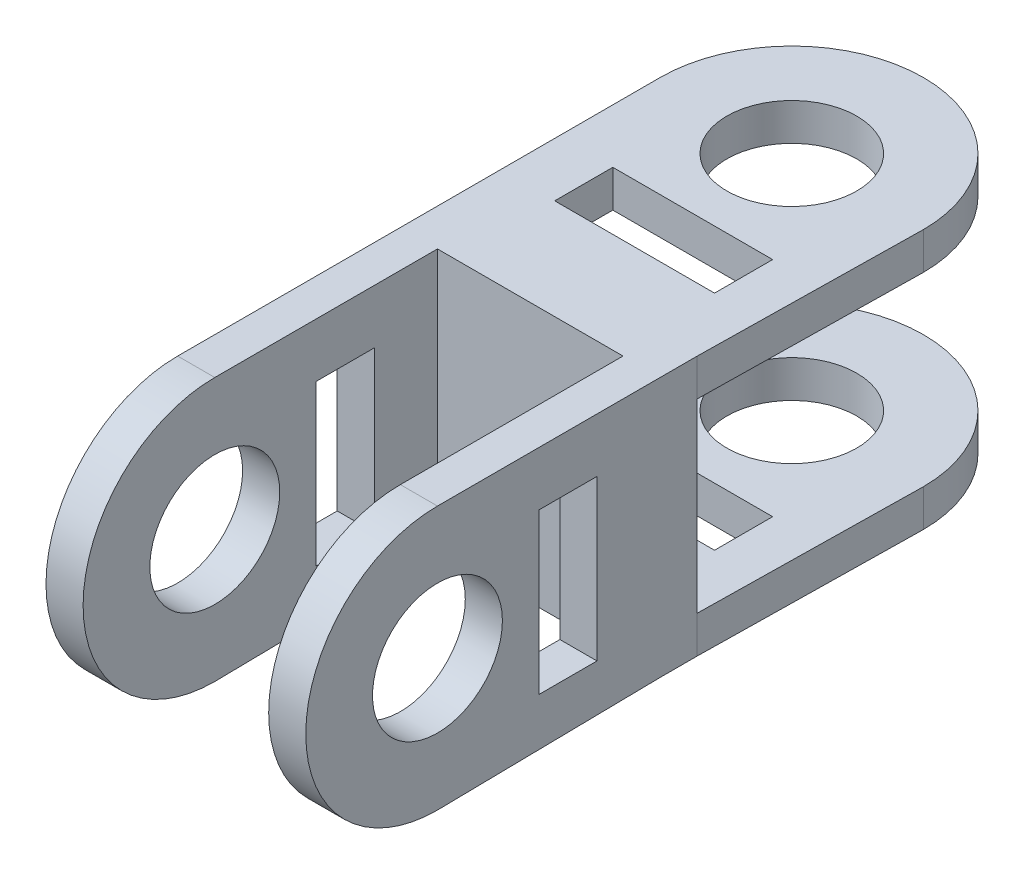
SolidWorks part; units mm, degrees
ref_plane "前基準面" through (0, 0, 0) normal (0, 0, 1) x (1, 0, 0)
ref_plane "上基準面" through (0, 0, 0) normal (0, 1, 0) x (1, 0, 0)
ref_plane "右基準面" through (0, 0, 0) normal (1, 0, 0) x (0, 0, -1)
sketch "草圖1" plane through (0, 0, 0) normal (0, 0, 1) x (1, 0, 0)
  line L1 (-35, 35) -> (35, 35)
  line L2 (-35, 35) -> (-35, -35)
  line L3 (-35, -35) -> (35, -35)
  line L4 (35, 35) -> (35, -35)
  dimension "D1" = 70
  dimension "D2" = 70
  dimension "D3" = 35
  dimension "D4" = 35
extrude "填料-伸長1" add sketch "草圖1" along normal blind 10
sketch "草圖2" plane through (0, 0, 0) normal (1, 0, 0) x (0, 0, -1)
  line L0 (-10, 35) -> (-70, 35)
  line L2 (-70, -35.9534) -> (-10, -35)
  line L3 (-10, -35) -> (-10, 35)
  line L5 (-42.6735, 20.4226) -> (-27.0133, 20.4226)
  line L6 (-42.6735, 20.4226) -> (-42.6735, -22.6429)
  line L7 (-42.6735, -22.6429) -> (-27.0133, -22.6429)
  line L8 (-27.0133, 20.4226) -> (-27.0133, -22.6429)
  arc A0 (-70, 35) -> (-70, -35.9534) centre (-70, -0.4767) ccw
  circle A1 centre (-70, -0.4767) radius 17.5
  dimension "D1" = 35
  dimension "D2" = 60
extrude "填料-伸長2" add sketch "草圖2" along normal mid plane 70
extrude "除料-伸長1" cut sketch "草圖2<2>" against normal mid plane 50
sketch "草圖2<2>" plane through (0, 0, 0) normal (1, 0, 0) x (0, 0, -1) same geometry as "草圖2"
sketch "草圖3" plane through (0, 0, 10) normal (0, -1, 0) x (0, 0, 1)
  line L0 (-10, 35) -> (-70, 35)
  line L2 (-70, -35.9534) -> (-10, -35)
  line L3 (-10, -35) -> (-10, 35)
  line L4 (-10, -35) -> (-10, 35) construction
  line L5 (-42.6735, 20.4226) -> (-27.0133, 20.4226)
  line L6 (-42.6735, 20.4226) -> (-42.6735, -22.6429)
  line L7 (-42.6735, -22.6429) -> (-27.0133, -22.6429)
  line L8 (-27.0133, 20.4226) -> (-27.0133, -22.6429)
  line L9 (60, 35) -> (-10, 35) construction
  arc A0 (-70, 35) -> (-70, -35.9534) centre (-70, -0.4767) ccw
  circle A1 centre (-70, -0.4767) radius 17.5
extrude "填料-伸長3" add sketch "草圖3" along normal mid plane 70
extrude "除料-伸長2" cut sketch "草圖3<3>" against normal mid plane 50
sketch "草圖3<3>" plane through (0, 0, 10) normal (0, -1, 0) x (0, 0, 1) same geometry as "草圖3"
